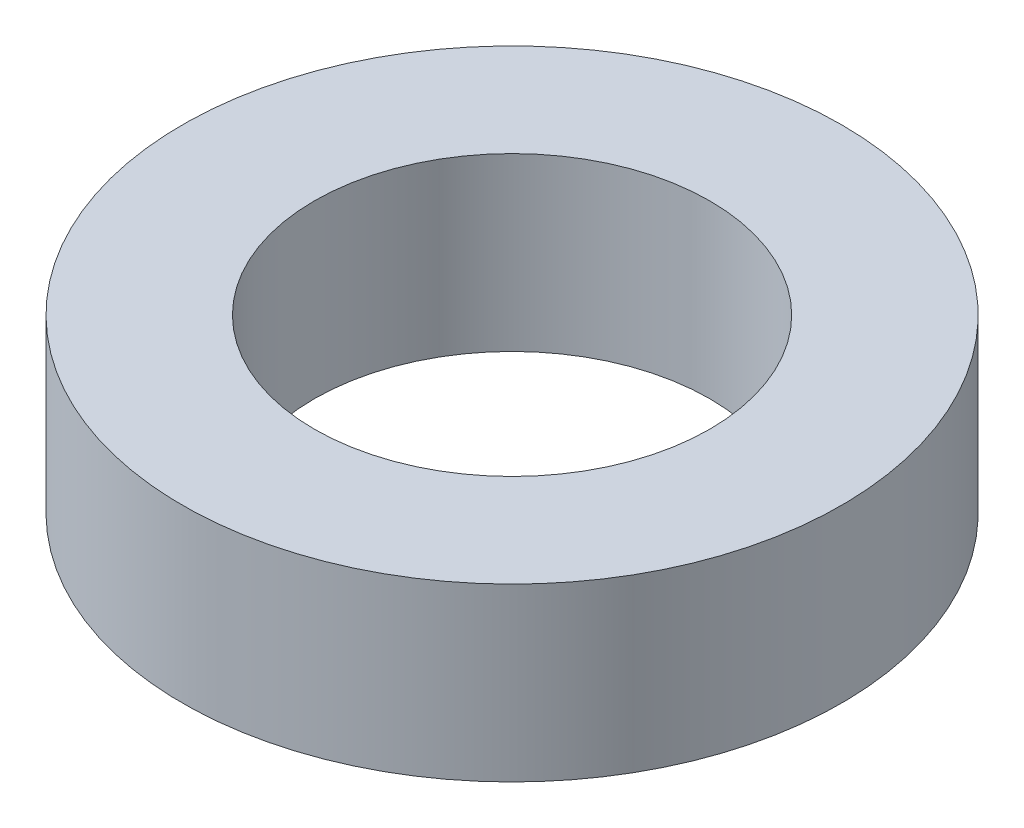
SolidWorks part; units mm, degrees
ref_plane "Front Plane" through (0, 0, 0) normal (0, 0, 1) x (1, 0, 0)
ref_plane "Top Plane" through (0, 0, 0) normal (0, 1, 0) x (1, 0, 0)
ref_plane "Right Plane" through (0, 0, 0) normal (1, 0, 0) x (0, 0, -1)
sketch "Sketch1" plane through (0, 0, 0) normal (0, 1, 0) x (1, 0, 0)
  circle A0 centre (0, 0) radius 50
  dimension "FLANGE_OD" = 100
extrude "Boss-Extrude1" add sketch "Sketch1" along normal blind 26
sketch "Sketch2" plane through (0, 0, 0) normal (0, 1, 0) x (1, 0, 0)
  circle A0 centre (0, 0) radius 30
  dimension "BORE_D" = 60
extrude "Cut-Extrude1" cut sketch "Sketch2" along normal through all
sketch "Sketch3" plane through (0, 26, 0) normal (0, 1, 0) x (1, 0, 0)
  circle A0 centre (0, 0) radius 21.1565 construction
  circle A1 centre (-21.1565, 0) radius 2.2822
  dimension "BOLT_D" = 4.5644
  dimension "BOLT_PCD" = 42.3129
extrude "Cut-Extrude2" cut sketch "Sketch3" against normal blind 22.8417 rebuild error yes
pattern_circular "CirPattern1" count 5 over 360 rebuild error yes
